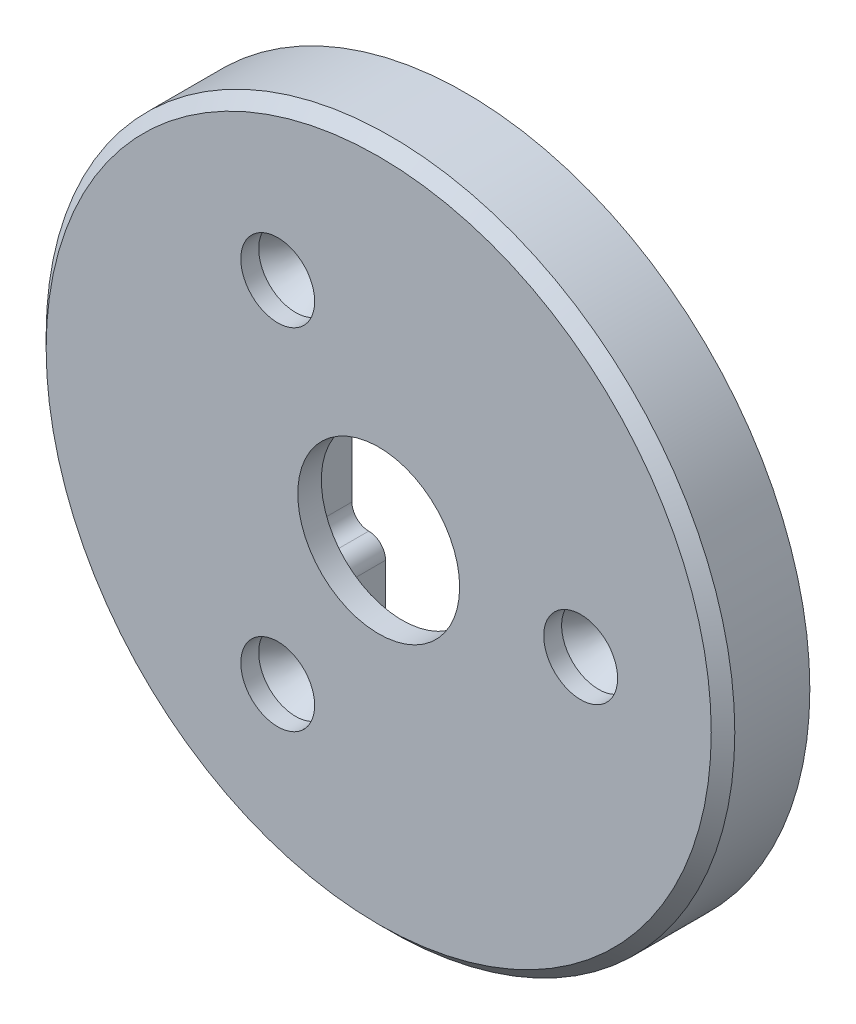
SolidWorks part; units mm, degrees
material "有机玻璃 (TM) GS 丙烯酸铸钣"
ref_plane "前视基准面" through (0, 0, 0) normal (0, 0, 1) x (1, 0, 0)
ref_plane "上视基准面" through (0, 0, 0) normal (0, 1, 0) x (1, 0, 0)
ref_plane "右视基准面" through (0, 0, 0) normal (1, 0, 0) x (0, 0, -1)
sketch "草图2" plane through (0, 0, 0) normal (0, 0, 1) x (1, 0, 0)
  circle A2 centre (100, 100) radius 21.6
sketch "草图3" plane through (0, 0, 0) normal (0, 0, 1) x (1, 0, 0)
  circle A0 centre (100, 100) radius 23.4
extrude "凸台-拉伸3" add sketch "草图3" along normal blind 5.9
extrude "切除-拉伸1" cut sketch "草图2" along normal blind 1.7
sketch "草图4" plane through (0, 0, 0) normal (0, 0, 1) x (1, 0, 0)
  line L0 (83.312, 98.171) -> (83.312, 101.854)
  line L1 (83.566, 97.917) -> (86.868, 97.917)
  line L2 (87.122, 98.171) -> (87.122, 101.727)
  line L3 (83.566, 102.108) -> (86.741, 102.108)
  line L4 (98.171, 114.173) -> (98.171, 115.57)
  line L5 (96.901, 114.173) -> (98.171, 114.173)
  line L6 (96.393, 106.045) -> (96.393, 113.665)
  line L7 (93.98, 97.155) -> (93.98, 103.632)
  line L8 (96.266, 83.693) -> (96.266, 94.869)
  line L9 (96.901, 83.058) -> (102.489, 83.058)
  line L10 (103.759, 84.328) -> (106.807, 84.328)
  line L11 (107.188, 84.709) -> (108.712, 84.709)
  line L12 (109.347, 85.344) -> (109.347, 86.868)
  line L13 (109.855, 87.376) -> (110.871, 87.376)
  line L14 (111.379, 87.884) -> (111.379, 88.646)
  line L15 (111.887, 89.154) -> (114.046, 89.154)
  line L16 (114.554, 89.662) -> (114.554, 91.059)
  line L17 (115.062, 91.567) -> (115.189, 91.567)
  line L18 (115.824, 92.202) -> (115.824, 94.615)
  line L19 (106.299, 94.869) -> (115.57, 94.869)
  line L20 (105.791, 95.377) -> (105.791, 102.616)
  line L21 (106.426, 103.251) -> (115.443, 103.251)
  line L22 (116.586, 102.108) -> (117.983, 102.108)
  line L23 (118.237, 102.362) -> (118.237, 102.997)
  line L24 (116.713, 104.521) -> (116.713, 109.093)
  line L25 (111.252, 109.855) -> (115.951, 109.855)
  line L26 (110.744, 110.363) -> (110.744, 113.411)
  line L27 (103.632, 114.427) -> (109.728, 114.427)
  line L28 (103.251, 114.808) -> (103.251, 115.57)
  line L29 (98.552, 115.951) -> (102.87, 115.951)
  arc A60 (83.566, 102.108) -> (83.312, 101.854) centre (83.566, 101.854) ccw
  arc A63 (83.312, 98.171) -> (83.566, 97.917) centre (83.566, 98.171) ccw
  arc A66 (86.868, 97.917) -> (87.122, 98.171) centre (86.868, 98.171) ccw
  arc A69 (87.122, 101.727) -> (86.741, 102.108) centre (86.741, 101.727) ccw
  arc A72 (98.552, 115.951) -> (98.171, 115.57) centre (98.552, 115.57) ccw
  arc A75 (96.901, 114.173) -> (96.393, 113.665) centre (96.901, 113.665) ccw
  arc A78 (95.25, 104.902) -> (96.393, 106.045) centre (95.25, 106.045) ccw
  arc A81 (95.25, 104.902) -> (93.98, 103.632) centre (95.25, 103.632) ccw
  arc A84 (93.98, 97.155) -> (95.123, 96.012) centre (95.123, 97.155) ccw
  arc A87 (96.266, 94.869) -> (95.123, 96.012) centre (95.123, 94.869) ccw
  arc A90 (96.266, 83.693) -> (96.901, 83.058) centre (96.901, 83.693) ccw
  arc A93 (102.489, 83.058) -> (102.87, 83.439) centre (102.489, 83.439) ccw
  arc A96 (103.759, 84.328) -> (102.87, 83.439) centre (103.759, 83.439) ccw
  arc A99 (106.807, 84.328) -> (106.934, 84.455) centre (106.807, 84.455) ccw
  arc A102 (107.188, 84.709) -> (106.934, 84.455) centre (107.188, 84.455) ccw
  arc A105 (108.712, 84.709) -> (109.347, 85.344) centre (108.712, 85.344) ccw
  arc A108 (109.855, 87.376) -> (109.347, 86.868) centre (109.855, 86.868) ccw
  arc A111 (110.871, 87.376) -> (111.379, 87.884) centre (110.871, 87.884) ccw
  arc A114 (111.887, 89.154) -> (111.379, 88.646) centre (111.887, 88.646) ccw
  arc A117 (114.046, 89.154) -> (114.554, 89.662) centre (114.046, 89.662) ccw
  arc A120 (115.062, 91.567) -> (114.554, 91.059) centre (115.062, 91.059) ccw
  arc A123 (115.189, 91.567) -> (115.824, 92.202) centre (115.189, 92.202) ccw
  arc A126 (115.824, 94.615) -> (115.57, 94.869) centre (115.57, 94.615) ccw
  arc A129 (105.791, 95.377) -> (106.299, 94.869) centre (106.299, 95.377) ccw
  arc A132 (106.426, 103.251) -> (105.791, 102.616) centre (106.426, 102.616) ccw
  arc A135 (116.078, 102.616) -> (115.443, 103.251) centre (115.443, 102.616) ccw
  arc A138 (116.078, 102.616) -> (116.586, 102.108) centre (116.586, 102.616) ccw
  arc A141 (117.983, 102.108) -> (118.237, 102.362) centre (117.983, 102.362) ccw
  arc A144 (118.237, 102.997) -> (117.729, 103.505) centre (117.729, 102.997) ccw
  arc A147 (116.713, 104.521) -> (117.729, 103.505) centre (117.729, 104.521) ccw
  arc A150 (116.713, 109.093) -> (115.951, 109.855) centre (115.951, 109.093) ccw
  arc A153 (110.744, 110.363) -> (111.252, 109.855) centre (111.252, 110.363) ccw
  arc A156 (110.744, 113.411) -> (109.728, 114.427) centre (109.728, 113.411) ccw
  arc A159 (103.251, 114.808) -> (103.632, 114.427) centre (103.632, 114.808) ccw
  arc A162 (103.251, 115.57) -> (102.87, 115.951) centre (102.87, 115.57) ccw
extrude "切除-拉伸2" cut sketch "草图4" along normal blind 2.6 from surface contours A162 L29 A72 L4 L5 A75 L6 A78 A81 L7 A84 A87 L8 A90 L9 A93 A96 L10 A99 A102 L11 A105 L12 A108 L13 region at (104.0257, 99.7178, 0) starting at face at (121.6, 100, 1.7)
sketch "草图5" plane through (0, 0, 0) normal (0, 0, 1) x (1, 0, 0)
  circle A0 centre (113.725, 100) radius 1.26
  circle A3 centre (93.1375, 88.1138) radius 1.26
  circle A6 centre (93.1375, 111.8862) radius 1.26
  circle A9 centre (100, 100) radius 5.5
extrude "切除-拉伸3" cut sketch "草图5" along normal up to surface (5.9 mm away) from surface contours A0 | A6 | A3 | A6 region at (113.725, 100, 0) region at (93.1375, 88.1138, 0) region at (93.1375, 111.8862, 0) up to face at (123.4, 100, 5.9) starting at face at (121.6, 100, 1.7)
extrude "切除-拉伸4" cut sketch "草图5<3>" along normal up to surface (5.9 mm away) from surface contours A9 region at (100, 100, 0) up to face at (114.985, 100, 5.9) starting at face at (107.6312, 98.717, 4.3)
sketch "草图5<3>" plane through (0, 0, 0) normal (0, 0, 1) x (1, 0, 0) same geometry as "草图5"
chamfer "倒角1" distance 0.8 angle 45 1 edges at (123.4, 100, 5.9)
sketch "草图6" plane through (0, 0, 0) normal (0, 0, 1) x (1, 0, 0)
  circle A0 centre (93.1375, 111.8862) radius 2.51
  circle A1 centre (93.1375, 88.1138) radius 2.51
  circle A2 centre (113.725, 100) radius 2.51
extrude "切除-拉伸5" cut sketch "草图6" against normal blind 1.2 from surface starting at face at (122.6, 100, 5.9)
chamfer "倒角2" distance 1.26 distance2 2 3 edges at (114.985, 100, 4.7) (94.3975, 88.1138, 4.7) (94.3975, 111.8862, 4.7) first distance on face at (114.985, 100, 4.7) first distance on face at (94.3975, 88.1138, 4.7) first distance on face at (94.3975, 111.8862, 4.7)
extrude "切除-拉伸6" cut sketch "草图4<3>" along normal blind 1.5 from surface contours L2 A69 L3 A60 L0 A63 L1 A66 region at (85.215, 100.0103, 0) starting at face at (114.985, 100, 1.7)
sketch "草图4<3>" plane through (0, 0, 0) normal (0, 0, 1) x (1, 0, 0) same geometry as "草图4"
